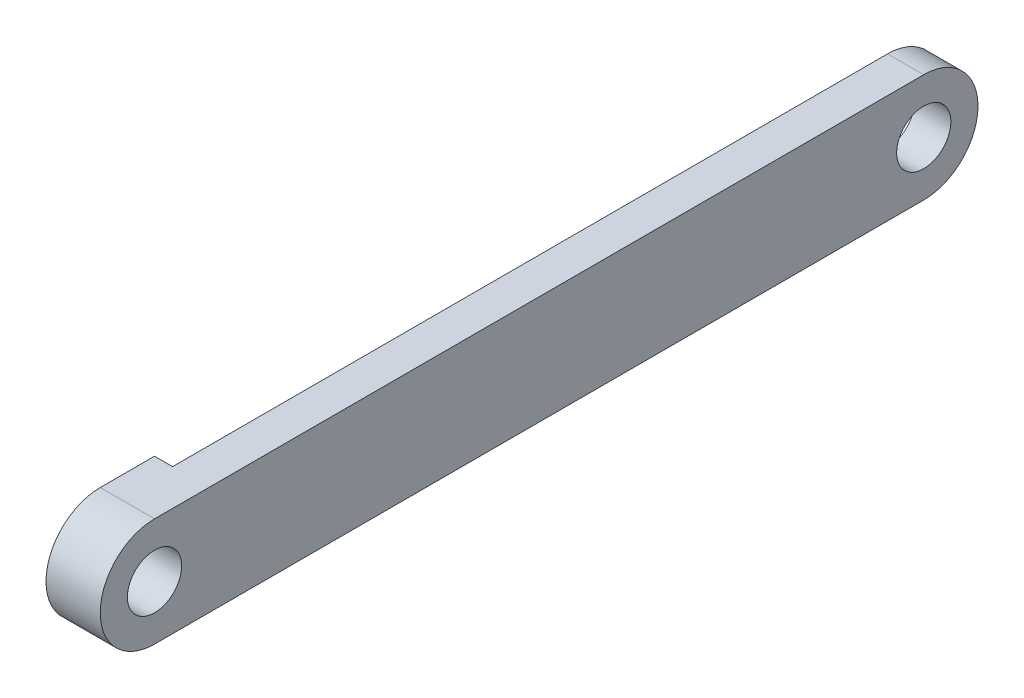
SolidWorks part; units mm, degrees
material "Plain Carbon Steel"
ref_plane "Front Plane" through (0, 0, 0) normal (0, 0, 1) x (1, 0, 0)
ref_plane "Top Plane" through (0, 0, 0) normal (0, 1, 0) x (1, 0, 0)
ref_plane "Right Plane" through (0, 0, 0) normal (1, 0, 0) x (0, 0, -1)
sketch "Sketch1" plane through (0, 0, 0) normal (1, 0, 0) x (0, 0, -1)
  line L0 (0, 0) -> (42.53, 0) construction
  line L1 (0, -3) -> (42.53, -3)
  line L18 (0, 3) -> (42.53, 3)
  arc A10 (0, -3) -> (0, 3) centre (0, 0) cw
  arc A11 (42.53, 3) -> (42.53, -3) centre (42.53, 0) cw
  circle A12 centre (0, 0) radius 1.5
  circle A13 centre (42.53, 0) radius 1.5
  dimension "D4" = 3
  dimension "D1" = 3
  dimension "D3" = 42.53
  dimension "D2" = 3
extrude "Boss-Extrude1" add sketch "Sketch1" along normal blind 3
sketch "Sketch2" plane through (0, 0, 0) normal (-1, 0, 0) x (0, 0, 1)
  line L0 (0, -3) -> (-42.53, -3) construction
  line L1 (-45.53, 3) -> (-3, 3)
  line L2 (-45.53, 3) -> (-45.53, -3)
  line L3 (-45.53, -3) -> (-3, -3)
  line L4 (-3, 3) -> (-3, -3)
  line L5 (-42.53, 3) -> (0, 3) construction
  arc A0 (0, -3) -> (0, 3) centre (0, 0) ccw construction
  arc A1 (-42.53, 3) -> (-42.53, -3) centre (-42.53, 0) ccw construction
  point P9 (3, 0)
  dimension "D1" = 6
extrude "Cut-Extrude1" cut sketch "Sketch2" against normal blind 1 contours L1 L4 L3 L2
